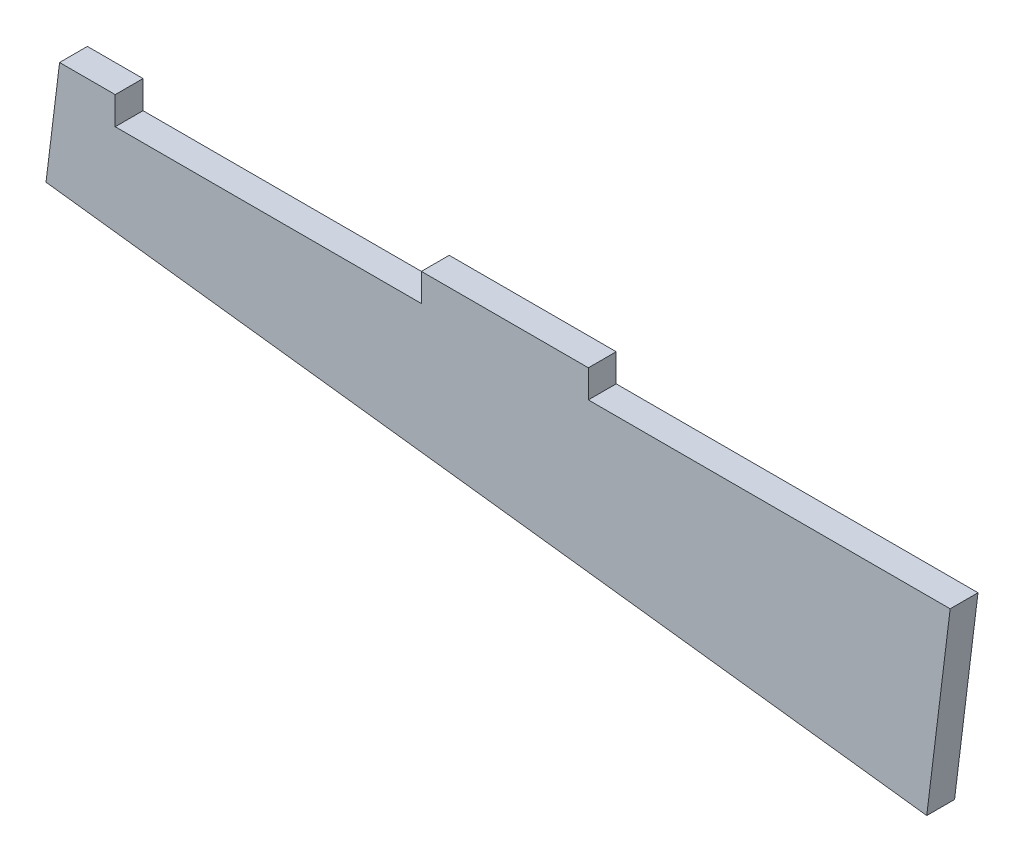
SolidWorks part; units mm, degrees
ref_plane "Front Plane" through (0, 0, 0) normal (0, 0, 1) x (1, 0, 0)
ref_plane "Top Plane" through (0, 0, 0) normal (0, 1, 0) x (1, 0, 0)
ref_plane "Right Plane" through (0, 0, 0) normal (1, 0, 0) x (0, 0, -1)
sketch "Sketch1" plane through (0, 0, 0) normal (0, 0, 1) x (1, 0, 0)
  line L0 (-195.3168, -62.6592) -> (-182.6168, -62.6592)
  line L4 (-182.6168, -62.6592) -> (-182.6168, -69.0092)
  line L5 (-182.6168, -69.0092) -> (-112.7668, -69.0092)
  line L6 (-112.7668, -69.0092) -> (-112.7668, -62.6592)
  line L7 (-112.7668, -62.6592) -> (-74.6668, -62.6592)
  line L8 (-74.6668, -62.6592) -> (-74.6668, -69.0092)
  line L9 (-74.6668, -69.0092) -> (7.8832, -69.0092)
  line L10 (7.8832, -69.0092) -> (2.5379, -112.5435)
  line L11 (2.5379, -112.5435) -> (-198.4122, -87.8699)
  line L12 (-198.4122, -87.8699) -> (-195.3168, -62.6592)
  line L13 (-339.7788, -23.2066) -> (-320.8708, -25.5282) construction
  dimension "D1" = 12.7
  dimension "D2" = 6.35
  dimension "D3" = 69.85
  dimension "D4" = 38.1
  dimension "D5" = 82.55
  dimension "D6" = 25.4
extrude "Boss-Extrude1" add sketch "Sketch1" against normal blind 6.35
